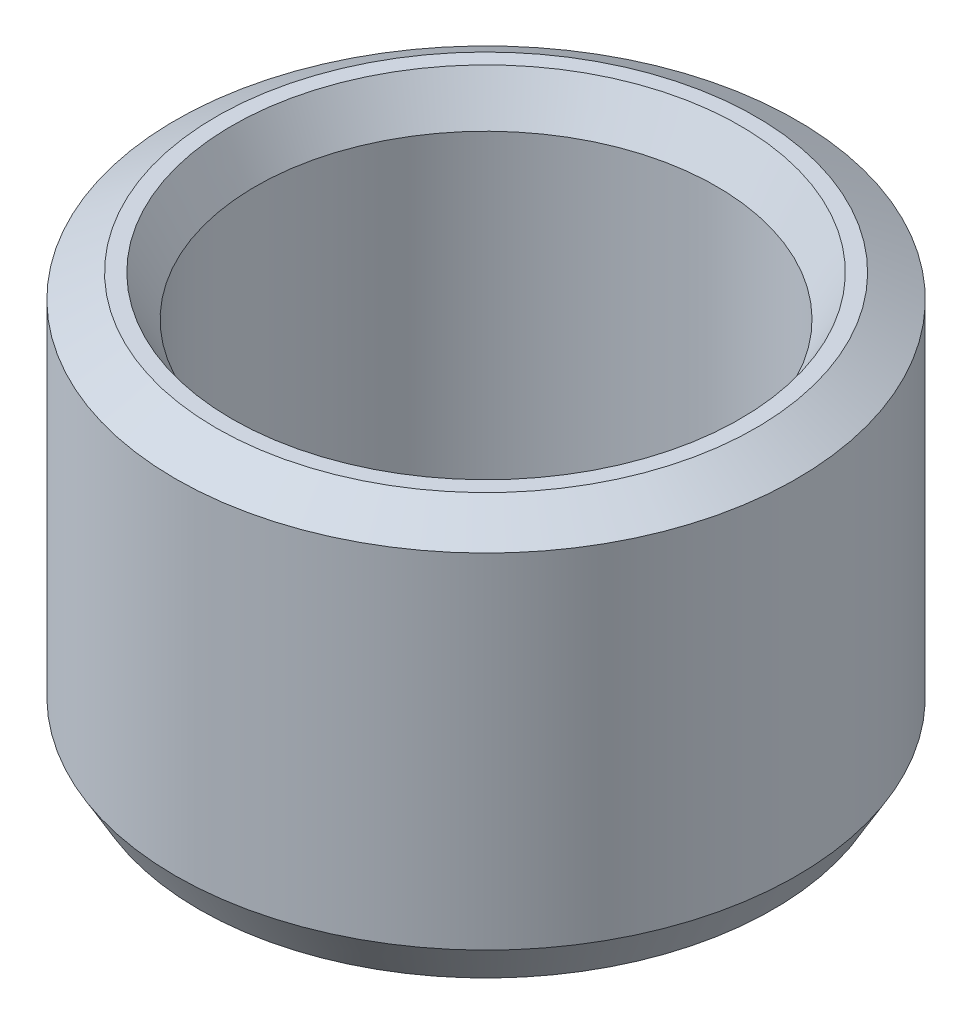
SolidWorks part; units mm, degrees
ref_plane "Front Plane" through (0, 0, 0) normal (0, 0, 1) x (1, 0, 0)
ref_plane "Top Plane" through (0, 0, 0) normal (0, 1, 0) x (1, 0, 0)
ref_plane "Right Plane" through (0, 0, 0) normal (1, 0, 0) x (0, 0, -1)
sketch "Sketch1" plane through (0, 0, 0) normal (0, 1, 0) x (1, 0, 0)
  circle A0 centre (0, 0) radius 27.5
  dimension "SLEEVE_OD" = 55
extrude "Boss-Extrude1" add sketch "Sketch1" along normal blind 36.143
sketch "Sketch2" plane through (0, 0, 0) normal (0, 1, 0) x (1, 0, 0)
  circle A0 centre (0, 0) radius 20.4091
  dimension "BORE_D" = 40.8183
extrude "Cut-Extrude1" cut sketch "Sketch2" along normal through all
chamfer "Chamfer1" distance 2.085 angle 60 4 edges at (0, 36.143, 20.4091) (0, 0, 20.4091) (0, 0, 27.5) (0, 36.143, 27.5) first distance on face at (0, 36.143, 20.4091) first distance on face at (0, 0, 20.4091) first distance on face at (0, 36.143, 27.5)
